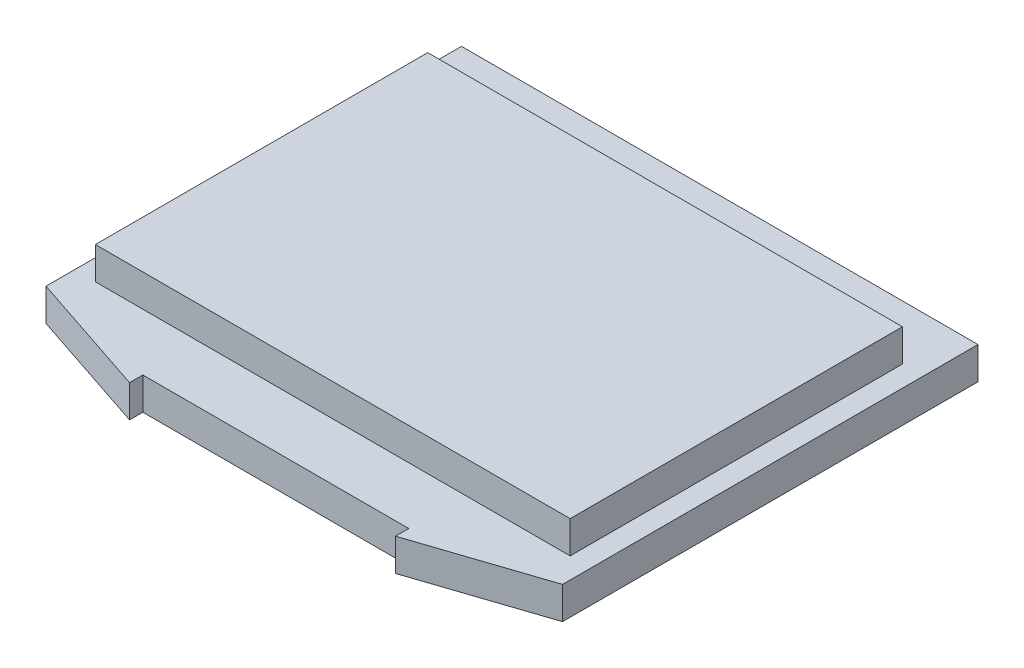
SolidWorks part; units mm, degrees
ref_plane "Front Plane" through (0, 0, 0) normal (0, 0, 1) x (1, 0, 0)
ref_plane "Top Plane" through (0, 0, 0) normal (0, 1, 0) x (1, 0, 0)
ref_plane "Right Plane" through (0, 0, 0) normal (1, 0, 0) x (0, 0, -1)
sketch "Sketch1" plane through (0, 0, 0) normal (0, 1, 0) x (1, 0, 0)
  line L0 (-13.6, -14.25) -> (-7, -14.25)
  line L1 (-13.6, -14.25) -> (13.6, -14.25) construction
  line L2 (-13.6, -14.25) -> (-13.6, 14.25)
  line L3 (-13.6, 14.25) -> (13.6, 14.25)
  line L4 (13.6, -14.25) -> (13.6, 14.25)
  line L5 (-13.6, -14.25) -> (13.6, 14.25) construction
  line L6 (-13.6, 14.25) -> (13.6, -14.25) construction
  line L7 (-7, -14.25) -> (-7, -11.75)
  line L8 (-7, -11.75) -> (7, -11.75)
  line L9 (7, -11.75) -> (7, -14.25)
  line L10 (7, -14.25) -> (13.6, -14.25)
  point P0 (0, 0)
  dimension "D1" = 27.2
  dimension "D2" = 28.5
  dimension "D3" = 2.5
  dimension "D4" = 14
extrude "Boss-Extrude1" add sketch "Sketch1" along normal blind 1.7
sketch "Sketch2" plane through (0, 1.7, 0) normal (0, 1, 0) x (1, 0, 0)
  line L1 (-12.5, -8.75) -> (12.5, -8.75)
  line L2 (-12.5, -8.75) -> (-12.5, 8.75)
  line L3 (-12.5, 8.75) -> (12.5, 8.75)
  line L4 (12.5, -8.75) -> (12.5, 8.75)
  line L5 (-12.5, -8.75) -> (12.5, 8.75) construction
  line L6 (-12.5, 8.75) -> (12.5, -8.75) construction
  point P0 (0, 0)
  dimension "D1" = 25
  dimension "D2" = 17.5
extrude "Boss-Extrude2" add sketch "Sketch2" along normal blind 1.7
chamfer "Chamfer1" distance 4 distance2 12 1 edges at (-13.6, 0.85, 14.25) first distance on face at (-13.6, 0.85, 0)
chamfer "Chamfer2" distance 12 distance2 4 1 edges at (13.6, 0.85, 14.25) first distance on face at (10.3, 0.85, 14.25)
sketch "Sketch3" plane through (0, 1.7, 0) normal (0, 1, 0) x (1, 0, 0)
  line L0 (13.6, -10.25) -> (13.6, 14.25) construction
  line L1 (-13.6, 14.25) -> (13.6, 14.25)
  line L2 (-13.6, 14.25) -> (-13.6, 11.628)
  line L3 (-13.6, 11.628) -> (13.6, 11.628)
  line L4 (13.6, 14.25) -> (13.6, 11.628)
extrude "Cut-Extrude1" cut sketch "Sketch3" against normal through all
